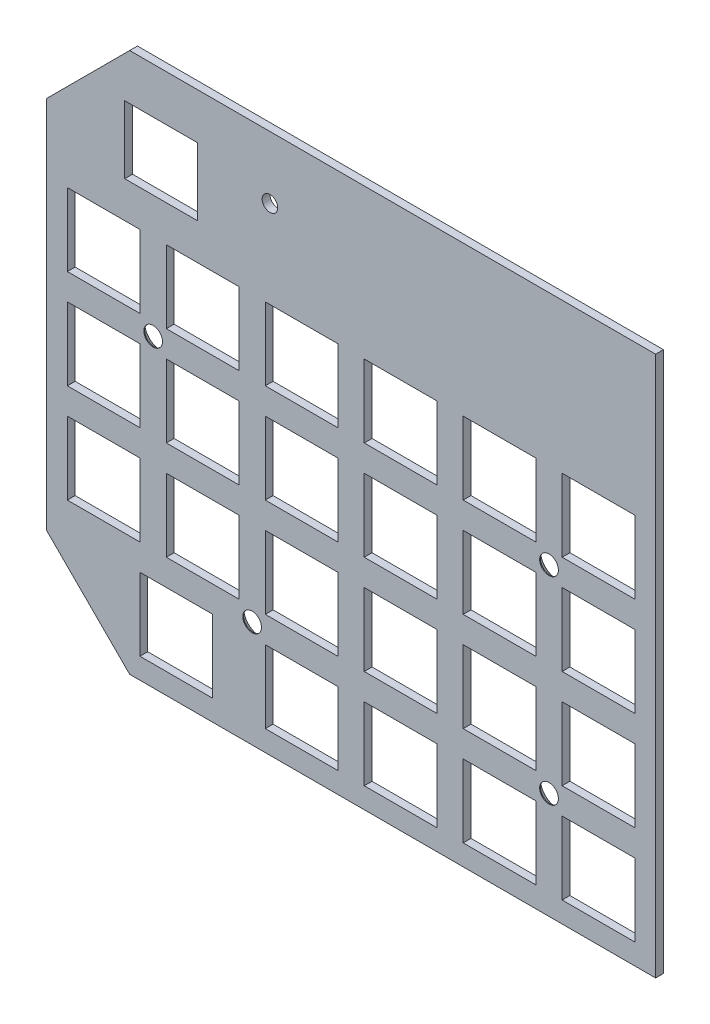
SolidWorks part; units mm, degrees
material "Alliage 1060"
ref_plane "Plan de face" through (0, 0, 0) normal (0, 0, 1) x (1, 0, 0)
ref_plane "Plan de dessus" through (0, 0, 0) normal (0, 1, 0) x (1, 0, 0)
ref_plane "Plan de droite" through (0, 0, 0) normal (1, 0, 0) x (0, 0, -1)
sketch "Esquisse1" plane through (0, 0, 0) normal (0, 0, 1) x (1, 0, 0)
  line L0 (0, -85) -> (16, -101)
  line L4 (117.25, 3) -> (117.25, -101)
  line L5 (16, 3) -> (0, -13)
  line L7 (117.25, 3) -> (16, 3)
  line L8 (0, -13) -> (0, -85)
  line L9 (16, -101) -> (117.25, -101)
  dimension "D1" = 104
  dimension "D2" = 117.25
  dimension "D3" = 16
  dimension "D4" = 16
  dimension "D5" = 16
  dimension "D6" = 16
extrude "Boss.-Extru.1" add sketch "Esquisse1" along normal blind 1.5
sketch "Esquisse3" plane through (0, 0, 0) normal (0, 0, -1) x (-1, 0, 0)
  line L0 (-94.2, -25.85) -> (-94.2, -39.85)
  line L1 (-113.25, -25.85) -> (-99.25, -25.85)
  line L2 (-113.25, -25.85) -> (-113.25, -39.85)
  line L3 (-113.25, -39.85) -> (-99.25, -39.85)
  line L4 (-99.25, -25.85) -> (-99.25, -39.85)
  line L5 (-106.25, -39.85) -> (-106.25, -25.85) construction
  line L6 (-113.25, -32.85) -> (-99.25, -32.85) construction
  line L7 (-94.2, -25.85) -> (-80.2, -25.85)
  line L8 (-80.2, -25.85) -> (-80.2, -39.85)
  line L9 (-94.2, -39.85) -> (-80.2, -39.85)
  line L10 (-75.15, -25.85) -> (-75.15, -39.85)
  line L11 (-75.15, -25.85) -> (-61.15, -25.85)
  line L12 (-61.15, -25.85) -> (-61.15, -39.85)
  line L13 (-75.15, -39.85) -> (-61.15, -39.85)
  line L14 (-56.1, -25.85) -> (-56.1, -39.85)
  line L15 (-56.1, -25.85) -> (-42.1, -25.85)
  line L16 (-42.1, -25.85) -> (-42.1, -39.85)
  line L17 (-56.1, -39.85) -> (-42.1, -39.85)
  line L18 (-37.05, -25.85) -> (-37.05, -39.85)
  line L19 (-37.05, -25.85) -> (-23.05, -25.85)
  line L20 (-23.05, -25.85) -> (-23.05, -39.85)
  line L21 (-37.05, -39.85) -> (-23.05, -39.85)
  line L22 (-18, -25.85) -> (-18, -39.85)
  line L23 (-18, -25.85) -> (-4, -25.85)
  line L24 (-4, -25.85) -> (-4, -39.85)
  line L25 (-18, -39.85) -> (-4, -39.85)
  line L26 (-94.2, -44.9) -> (-94.2, -58.9)
  line L27 (-94.2, -44.9) -> (-80.2, -44.9)
  line L28 (-80.2, -44.9) -> (-80.2, -58.9)
  line L29 (-94.2, -58.9) -> (-80.2, -58.9)
  line L30 (-75.15, -44.9) -> (-75.15, -58.9)
  line L31 (-75.15, -44.9) -> (-61.15, -44.9)
  line L32 (-61.15, -44.9) -> (-61.15, -58.9)
  line L33 (-75.15, -58.9) -> (-61.15, -58.9)
  line L34 (-56.1, -44.9) -> (-56.1, -58.9)
  line L35 (-56.1, -44.9) -> (-42.1, -44.9)
  line L36 (-42.1, -44.9) -> (-42.1, -58.9)
  line L37 (-56.1, -58.9) -> (-42.1, -58.9)
  line L38 (-37.05, -44.9) -> (-37.05, -58.9)
  line L39 (-37.05, -44.9) -> (-23.05, -44.9)
  line L40 (-23.05, -44.9) -> (-23.05, -58.9)
  line L41 (-37.05, -58.9) -> (-23.05, -58.9)
  line L42 (-18, -44.9) -> (-18, -58.9)
  line L43 (-18, -44.9) -> (-4, -44.9)
  line L44 (-4, -44.9) -> (-4, -58.9)
  line L45 (-18, -58.9) -> (-4, -58.9)
  line L46 (-94.2, -63.95) -> (-94.2, -77.95)
  line L47 (-94.2, -63.95) -> (-80.2, -63.95)
  line L48 (-80.2, -63.95) -> (-80.2, -77.95)
  line L49 (-94.2, -77.95) -> (-80.2, -77.95)
  line L50 (-75.15, -63.95) -> (-75.15, -77.95)
  line L51 (-75.15, -63.95) -> (-61.15, -63.95)
  line L52 (-61.15, -63.95) -> (-61.15, -77.95)
  line L53 (-75.15, -77.95) -> (-61.15, -77.95)
  line L54 (-56.1, -63.95) -> (-56.1, -77.95)
  line L55 (-56.1, -63.95) -> (-42.1, -63.95)
  line L56 (-42.1, -63.95) -> (-42.1, -77.95)
  line L57 (-56.1, -77.95) -> (-42.1, -77.95)
  line L58 (-37.05, -63.95) -> (-37.05, -77.95)
  line L59 (-37.05, -63.95) -> (-23.05, -63.95)
  line L60 (-23.05, -63.95) -> (-23.05, -77.95)
  line L61 (-37.05, -77.95) -> (-23.05, -77.95)
  line L62 (-18, -63.95) -> (-18, -77.95)
  line L63 (-18, -63.95) -> (-4, -63.95)
  line L64 (-4, -63.95) -> (-4, -77.95)
  line L65 (-18, -77.95) -> (-4, -77.95)
  line L66 (-94.2, -83) -> (-94.2, -97)
  line L67 (-94.2, -83) -> (-80.2, -83)
  line L68 (-80.2, -83) -> (-80.2, -97)
  line L69 (-94.2, -97) -> (-80.2, -97)
  line L70 (-75.15, -83) -> (-75.15, -97)
  line L71 (-75.15, -83) -> (-61.15, -83)
  line L72 (-61.15, -83) -> (-61.15, -97)
  line L73 (-75.15, -97) -> (-61.15, -97)
  line L74 (-56.1, -83) -> (-56.1, -97)
  line L75 (-56.1, -83) -> (-42.1, -83)
  line L76 (-42.1, -83) -> (-42.1, -97)
  line L77 (-56.1, -97) -> (-42.1, -97)
  line L86 (-113.25, -44.9) -> (-113.25, -58.9)
  line L87 (-113.25, -44.9) -> (-99.25, -44.9)
  line L88 (-99.25, -44.9) -> (-99.25, -58.9)
  line L89 (-113.25, -58.9) -> (-99.25, -58.9)
  line L90 (-113.25, -63.95) -> (-113.25, -77.95)
  line L91 (-113.25, -63.95) -> (-99.25, -63.95)
  line L92 (-99.25, -63.95) -> (-99.25, -77.95)
  line L93 (-113.25, -77.95) -> (-99.25, -77.95)
  line L94 (-113.25, -83) -> (-113.25, -97)
  line L95 (-113.25, -83) -> (-99.25, -83)
  line L96 (-99.25, -83) -> (-99.25, -97)
  line L97 (-113.25, -97) -> (-99.25, -97)
  line L98 (-4, -83) -> (-4, -97) [skipped]
  line L99 (-18, -97) -> (-4, -97) [skipped]
  line L100 (-18, -83) -> (-18, -97) [skipped]
  line L101 (-18, -83) -> (-4, -83) [skipped]
  line L103 (-117.25, -101) -> (-117.25, 3) construction
  line L104 (-16, -101) -> (-117.25, -101) construction
  line L107 (-37.05, -83) -> (-23.05, -83) [skipped]
  line L108 (-23.05, -83) -> (-23.05, -97) [skipped]
  line L109 (-37.05, -83) -> (-37.05, -97) [skipped]
  line L110 (-37.05, -97) -> (-23.05, -97) [skipped]
  line L111 (0, -13) -> (0, -85) construction
  line L112 (-31.97, -83) -> (-17.97, -83)
  line L113 (-31.97, -83) -> (-31.97, -97)
  line L114 (-31.97, -97) -> (-17.97, -97)
  line L115 (-17.97, -83) -> (-17.97, -97)
  line L116 (-24.97, -97) -> (-24.97, -83) construction
  line L117 (-31.97, -90) -> (-17.97, -90) construction
  line L118 (-29.05, -5.85) -> (-15.05, -5.85)
  line L119 (-29.05, -5.85) -> (-29.05, -18.85)
  line L120 (-29.05, -18.85) -> (-15.05, -18.85)
  line L121 (-15.05, -5.85) -> (-15.05, -18.85)
  line L122 (-117.25, 3) -> (-16, 3) construction
  circle A5 centre (-43, -9) radius 1.5
  point P0 (-106.25, -32.85)
  point P84 (-24.97, -90)
  dimension "D7" = 43
  dimension "D8" = 12
  dimension "D1" = 14
  dimension "D2" = 14
  dimension "D5" = 4
  dimension "D6" = 4
  dimension "D9" = 5.05
  dimension "D10" = 14
  dimension "D11" = 14
  dimension "D12" = 10.13
  dimension "D13" = 5.05
  dimension "D14" = 14
  dimension "D15" = 7
  dimension "D16" = 13
  dimension "D17" = 6
  dimension "D3" = 6
  dimension "D4" = 4
extrude "Enlèv. mat.-Extru.2" cut sketch "Esquisse3" against normal blind 10
sketch "Esquisse4" plane through (0, 0, 0) normal (0, 0, -1) x (-1, 0, 0)
  line L0 (-99.25, -39.85) -> (-94.2, -44.9) construction
  line L1 (-23.05, -39.85) -> (-18, -44.9) construction
  line L2 (-37.05, -77.95) -> (-42.1, -83) construction
  line L3 (-94.2, -77.95) -> (-99.25, -83) construction
  point P16 (-96.725, -42.375)
  point P17 (-96.725, -80.475)
  point P18 (-39.575, -80.475)
hole_wizard "Fraisage pour vis à tête fraisée M31" positions "Esquisse5" profile "Esquisse6" countersink size "M3" standard "Ansi Metric" end condition through all
sketch "Esquisse5" plane through (0, 0, 0) normal (0, 0, -1) x (-1, 0, 0)
  line L0 (-23.05, -39.85) -> (-18, -44.9) construction
  line L1 (-37.05, -77.95) -> (-42.1, -83) construction
  point P0 (-96.725, -42.375)
  point P3 (-96.725, -80.475)
  point P6 (-20.525, -42.375)
  point P10 (-39.575, -80.475)
sketch "Esquisse6" plane through (96.725, -42.375, 0) normal (1, 0, 0) x (0, 1, 0)
  line L0 (0, 0) -> (0, 1.5)
  line L1 (0, 1.5) -> (1.8, 1.5)
  line L2 (1.8, 1.5) -> (1.8, 1.35)
  line L3 (1.8, 1.35) -> (3.15, 0)
  line L5 (3.15, 0) -> (0, 0)
  line L6 (-1.8, 1.35) -> (-3.15, 0) construction
  line L11 (0, -6.35) -> (0, 107.95) construction
  dimension "Diamètre du perçage jusqu'au prochain" = 3.6
  dimension "Profondeur du perçage jusqu'au prochain" = 1.5
  dimension "Diamètre du fraisage entrant" = 6.3
  dimension "Angle du fraisage entrant" = 90
